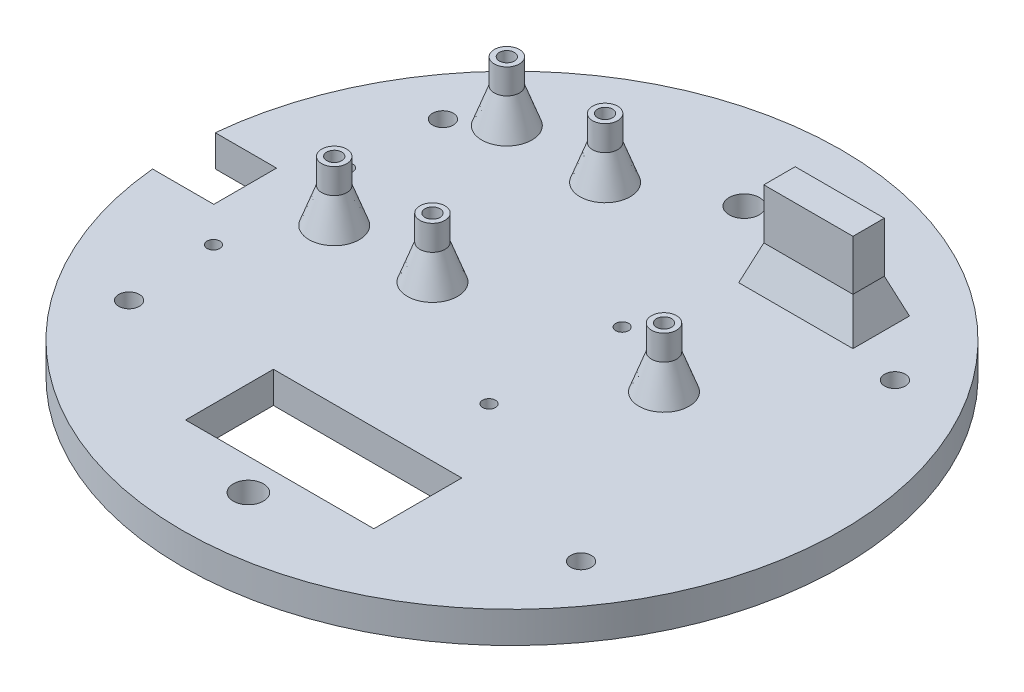
SolidWorks part; units mm, degrees
ref_plane "Front Plane" through (0, 0, 0) normal (0, 0, 1) x (1, 0, 0)
ref_plane "Top Plane" through (0, 0, 0) normal (0, 1, 0) x (1, 0, 0)
ref_plane "Right Plane" through (0, 0, 0) normal (1, 0, 0) x (0, 0, -1)
sketch "Sketch2" plane through (0, 0, 0) normal (0, 1, 0) x (1, 0, 0)
  line L0 (0, 0) -> (9.1621, 0) construction
  line L1 (0, 0) -> (0, 13.2968) construction
  line L3 (-15, -23) -> (15, -23)
  line L4 (-15, -23) -> (-15, -37)
  line L5 (-15, -37) -> (15, -37)
  line L6 (15, -23) -> (15, -37)
  line L7 (-15, -23) -> (15, -37) construction
  line L8 (-15, -37) -> (15, -23) construction
  circle A0 centre (0, 0) radius 52.5
  point P5 (0, -30)
  dimension "D1" = 105
  dimension "D2" = 14
  dimension "D3" = 30
  dimension "D4" = 30
extrude "Boss-Extrude1" add sketch "Sketch2" along normal blind 5
sketch "Sketch3" plane through (0, 0, 0) normal (0, -1, 0) x (1, 0, 0)
  line L0 (-15, 0) -> (-15, 12.9052) construction
  line L5 (0, 0) -> (14.6599, 0) construction
  circle A0 centre (-36.95, 10.6) radius 2.5 construction
  circle A4 centre (-36.95, -10.6) radius 2.5 construction
  circle A5 centre (6.95, -10.6) radius 2.5 construction
  circle A6 centre (6.95, 10.6) radius 2.5 construction
  point P0 (0, 0)
  dimension "D3" = 5
  dimension "D1" = 10.6
  dimension "D2" = 21.95
  dimension "D10" = 15
sketch "Sketch15" plane through (0, 5, 0) normal (0, 1, 0) x (1, 0, 0)
  line L0 (-22.2011, 29.3371) -> (-22.2011, 35.4897) construction
  line L7 (-21.0891, 15.4599) -> (-18.0632, 15.4599) construction
  circle A0 centre (-30.0261, 29.2099) radius 2
  circle A1 centre (-14.3761, 29.2099) radius 2
  circle A2 centre (-14.3761, 1.7099) radius 2
  circle A3 centre (-30.0261, 1.7099) radius 2
  dimension "D3" = 4
  dimension "D6" = 7.825
  dimension "D5" = 15.4599
  dimension "D7" = 13.75
  dimension "D1" = 13.75
  dimension "D2" = 22.2011
  dimension "D4" = 7.825
extrude "Boss-Extrude3" add sketch "Sketch15" along normal blind 9.5
sketch "Sketch17" plane through (0, 5, 0) normal (0, 1, 0) x (1, 0, 0)
  line L1 (12.1174, 33) -> (26.3174, 33)
  line L2 (12.1174, 33) -> (12.1174, 28)
  line L3 (12.1174, 28) -> (26.3174, 28)
  line L4 (26.3174, 33) -> (26.3174, 28)
  line L5 (12.1174, 33) -> (26.3174, 28) construction
  line L6 (12.1174, 28) -> (26.3174, 33) construction
  circle A0 centre (19.2174, 5) radius 2
  point P2 (19.2174, 30.5)
  dimension "D1" = 4
  dimension "D2" = 5
  dimension "D3" = 19.2174
  dimension "D4" = 23
  dimension "D5" = 14.2
  dimension "D6" = 5
extrude "Boss-Extrude4" add sketch "Sketch17" along normal blind 9.5
hole_wizard "M2 Clearance Hole2" positions "3DSketch11" profile "Sketch18" hole size "M2" standard "DIN"
sketch3d "3DSketch11"
  line L0 (19.2174, 14.5, -5) -> (19.2174, 5, -5) construction
  point P0 (19.2174, 14.5, -5)
sketch "Sketch18" plane through (19.2174, 14.5, -5) normal (1, 0, 0) x (0, 0, 1)
  line L0 (0, 0) -> (0, 9.5)
  line L1 (0, 9.5) -> (1.2, 9.5)
  line L2 (1.2, 9.5) -> (1.2, 0)
  line L5 (1.2, 0) -> (0, 0)
  line L10 (0, 9.5) -> (-1.2, 9.5) construction
  line L11 (0, -6.35) -> (0, 107.95) construction
  dimension "Hole Dia." = 2.4
  dimension "Hole Depth" = 9.5
  dimension "Drill Angle" = 180
sketch "Sketch19" plane through (0, 14.5, 0) normal (0, 1, 0) x (1, 0, 0)
  line L0 (26.3174, 28) -> (26.3174, 33) construction
  line L1 (12.1174, 28) -> (26.3174, 28) construction
  line L2 (12.1174, 33) -> (12.1174, 28) construction
  line L3 (26.3174, 33) -> (12.1174, 33) construction
  line L4 (26.3174, 28) -> (26.3174, 33)
  line L5 (12.1174, 28) -> (26.3174, 28)
  line L6 (12.1174, 33) -> (12.1174, 28)
  line L7 (26.3174, 33) -> (12.1174, 33)
extrude "Boss-Extrude5" add sketch "Sketch19" along normal blind 4
sketch "Sketch21" plane through (0, 5, 0) normal (0, 1, 0) x (1, 0, 0)
  line L8 (0, 0) -> (25.1353, 0) construction
  line L13 (25.1353, 0) -> (0, 0) construction
  line L14 (0, 0) -> (0, 20.9244) construction
  line L15 (-42.5, 5) -> (-42.5, -5)
  line L16 (-42.5, 5) -> (-52.5, 5)
  line L17 (-42.5, -5) -> (-52.5, -5)
  line L18 (-52.5, 5) -> (-52.5, -5)
  circle A2 centre (0, 0) radius 52.5 construction
  point P10 (-42.5, 0)
  dimension "D1" = 10
  dimension "D2" = 10
  dimension "D3" = 0
extrude "Cut-Extrude1" cut sketch "Sketch21" against normal through all
sketch "Sketch30" plane through (0, 0, 0) normal (0, -1, 0) x (1, 0, 0)
  line L0 (0, 0) -> (0, 26.3182) construction
  line L1 (0, 0) -> (19.571, 0) construction
  circle A0 centre (-36, 25) radius 3 construction
  circle A1 centre (36, 25) radius 3 construction
  circle A2 centre (36, -25) radius 3 construction
  circle A3 centre (-36, -25) radius 3 construction
  dimension "D1" = 6
  dimension "D2" = 36
  dimension "D3" = 25
hole_wizard "M4 Clearance Hole2" positions "3DSketch18" profile "Sketch35" hole size "M4" standard "DIN" end condition through all
sketch3d "3DSketch18"
  point P0 (0, 0, 42)
  point P2 (0, 0, -37)
  dimension "D1" = 42
  dimension "D3" = 37
sketch "Sketch35" plane through (0, 0, 42) normal (1, 0, 0) x (0, 0, -1)
  line L0 (0, 0) -> (0, 18.5)
  line L1 (0, 18.5) -> (2.4, 18.5)
  line L2 (2.4, 18.5) -> (2.4, 0)
  line L5 (2.4, 0) -> (0, 0)
  line L11 (0, -6.35) -> (0, 107.95) construction
  dimension "Thru Hole Dia." = 4.8
  dimension "Thru Hole Depth" = 18.5
hole_wizard "Tap Drill for M4 Tap1" positions "3DSketch19" profile "Sketch36" hole size "M4" standard "DIN" end condition through all
sketch3d "3DSketch19"
  point P0 (-36, 0, 25)
  point P3 (36, 0, 25)
  point P6 (36, 0, -25)
  point P9 (-36, 0, -25)
sketch "Sketch36" plane through (-36, 0, 25) normal (1, 0, 0) x (0, 0, -1)
  line L0 (0, 0) -> (0, 18.5)
  line L1 (0, 18.5) -> (1.65, 18.5)
  line L2 (1.65, 18.5) -> (1.65, 0)
  line L5 (1.65, 0) -> (0, 0)
  line L11 (0, -6.35) -> (0, 107.95) construction
  dimension "Thru Hole Dia." = 3.3
  dimension "Thru Hole Depth" = 18.5
hole_wizard "Tap Drill for M2.5 Tap2" positions "3DSketch20" profile "Sketch37" hole size "M2.5" standard "DIN" end condition through all
sketch3d "3DSketch20"
  point P0 (-36.95, 0, 10.6)
  point P3 (6.95, 0, 10.6)
  point P6 (6.95, 0, -10.6)
  point P9 (-36.95, 0, -10.6)
sketch "Sketch37" plane through (-36.95, 0, 10.6) normal (1, 0, 0) x (0, 0, -1)
  line L0 (0, 0) -> (0, 18.5)
  line L1 (0, 18.5) -> (1.025, 18.5)
  line L2 (1.025, 18.5) -> (1.025, 0)
  line L5 (1.025, 0) -> (0, 0)
  line L11 (0, -6.35) -> (0, 107.95) construction
  dimension "Thru Hole Dia." = 2.05
  dimension "Thru Hole Depth" = 18.5
chamfer "Chamfer1" distance 2 angle 70 9 edges at (19.2174, 5, -3) (19.2174, 5, -28) (12.1174, 5, -30.5) (26.3174, 5, -30.5) (19.2174, 5, -33) (-14.3761, 5, 0.2901) (-14.3761, 5, -31.2099) (-30.0261, 5, -27.2099) (-30.0261, 5, -3.7099) first distance on face at (-36.95, 5, 11.625)
hole_wizard "M2 Clearance Hole1" positions "3DSketch24" profile "Sketch43" hole size "M2" standard "DIN"
sketch3d "3DSketch24"
  line L0 (-30.0261, 14.5, -29.2099) -> (-30.0261, 10.495, -29.2099) construction
  line L1 (-14.3761, 14.5, -29.2099) -> (-14.3761, 10.495, -29.2099) construction
  line L2 (-14.3761, 14.5, -1.7099) -> (-14.3761, 10.495, -1.7099) construction
  line L3 (-30.0261, 14.5, -1.7099) -> (-30.0261, 10.495, -1.7099) construction
  point P0 (-30.0261, 14.5, -29.2099)
  point P4 (-14.3761, 14.5, -29.2099)
  point P8 (-14.3761, 14.5, -1.7099)
  point P12 (-30.0261, 14.5, -1.7099)
sketch "Sketch43" plane through (-30.0261, 14.5, -29.2099) normal (1, 0, 0) x (0, 0, 1)
  line L0 (0, 0) -> (0, 9.5)
  line L1 (0, 9.5) -> (1.2, 9.5)
  line L2 (1.2, 9.5) -> (1.2, 0)
  line L5 (1.2, 0) -> (0, 0)
  line L10 (0, 9.5) -> (-1.2, 9.5) construction
  line L11 (0, -6.35) -> (0, 107.95) construction
  dimension "Hole Dia." = 2.4
  dimension "Hole Depth" = 9.5
  dimension "Drill Angle" = 180
sketch "Sketch54" plane through (0, 5, 0) normal (0, 1, 0) x (1, 0, 0)
  circle A0 centre (-30.0261, 29.2099) radius 0.8
  circle A1 centre (-14.3761, 29.2099) radius 0.8
  circle A2 centre (-14.3761, 1.7099) radius 0.8
  circle A3 centre (-30.0261, 1.7099) radius 0.8
  dimension "D1" = 1.6
  dimension "D2" = 1.6
  dimension "D3" = 1.6
  dimension "D4" = 1.6
extrude "Cut-Extrude2" cut sketch "Sketch54" against normal through all
sketch "Sketch56" plane through (0, 5, 0) normal (0, 1, 0) x (1, 0, 0)
  circle A0 centre (19.2174, 5) radius 0.8
  dimension "D1" = 1.6
extrude "Cut-Extrude3" cut sketch "Sketch56" against normal through all
equation "\"D2@Sketch54\"=\"D1@Sketch54\""
equation "\"D3@Sketch54\"=\"D1@Sketch54\""
equation "\"D4@Sketch54\"=\"D1@Sketch54\""
